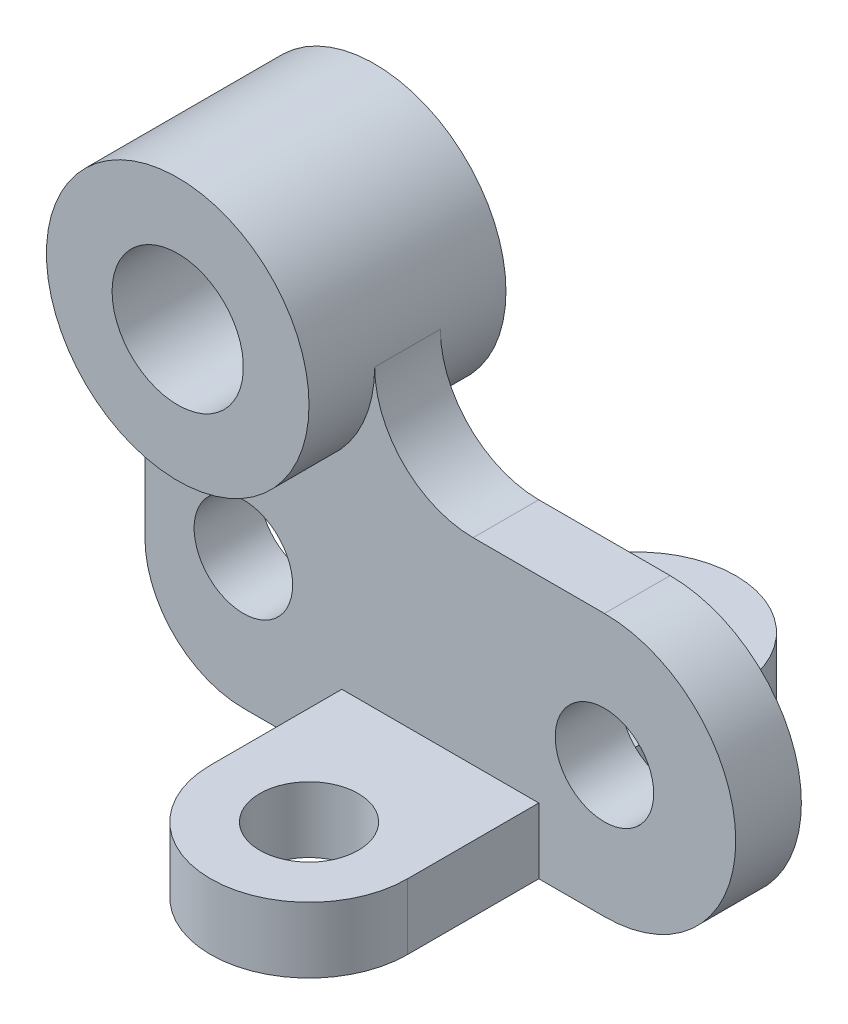
SolidWorks part; units mm, degrees
ref_plane "Front Plane" through (0, 0, 0) normal (0, 0, 1) x (1, 0, 0)
ref_plane "Top Plane" through (0, 0, 0) normal (0, 1, 0) x (1, 0, 0)
ref_plane "Right Plane" through (0, 0, 0) normal (1, 0, 0) x (0, 0, -1)
sketch "Sketch2" plane through (0, 0, 0) normal (0, 0, 1) x (1, 0, 0)
  line L0 (-19.05, -16.8005) -> (-19.05, -50.8)
  line L1 (0, -69.85) -> (69.85, -69.85)
  line L2 (44.45, -19.05) -> (69.85, -19.05)
  circle A0 centre (0, 0) radius 12.7
  circle A1 centre (0, 0) radius 25.4
  arc A2 (44.45, -19.05) -> (25.4, 0) centre (44.45, 0) cw
  arc A3 (69.85, -19.05) -> (69.85, -69.85) centre (69.85, -44.45) cw
  circle A4 centre (0, -44.45) radius 9.525
  circle A5 centre (69.85, -44.45) radius 9.525
  arc A6 (-19.05, -50.8) -> (0, -69.85) centre (0, -50.8) ccw
  point P15 (0, 0)
  point P16 (-19.0845, -16.7613)
  point P17 (0, 0)
  point P18 (0, 0)
  dimension "D1" = 25.4
  dimension "D2" = 50.8
  dimension "D3" = 88.9
  dimension "D5" = 25.4
  dimension "D6" = 19.05
  dimension "D7" = 19.05
  dimension "D9" = 19.05
  dimension "D4" = 44.45
  dimension "D8" = 69.85
extrude "Boss-Extrude1" add sketch "Sketch2" along normal mid plane 12.7 contours L0 A6 L1 A3 L2 A2 A1 A4 A5 region at (37.214, -44.0002, 0)
extrude "Boss-Extrude2" add sketch "Sketch2<3>" along normal mid plane 38.1 contours A1 A0 region at (-8.7263, 23.0875, 0)
sketch "Sketch2<3>" plane through (0, 0, 0) normal (0, 0, 1) x (1, 0, 0) same geometry as "Sketch2"
sketch "Sketch3" plane through (0, -69.85, 0) normal (0, -1, 0) x (1, 0, 0)
  line L0 (38.1, -31.75) -> (38.1, 31.75) construction
  line L1 (0, 6.35) -> (69.85, 6.35) construction
  line L2 (19.05, -31.75) -> (19.05, 31.75)
  line L3 (57.15, -31.75) -> (57.15, 31.75)
  line L4 (-122.4827, 0) -> (122.4827, 0) construction
  arc A0 (19.05, -31.75) -> (57.15, -31.75) centre (38.1, -31.75) ccw
  arc A1 (57.15, 31.75) -> (19.05, 31.75) centre (38.1, 31.75) ccw
  circle A2 centre (38.1, 31.75) radius 9.525
  circle A3 centre (38.1, -31.75) radius 9.525
  point P4 (38.1, 0)
  point P13 (0, 0)
  dimension "D1" = 19.05
  dimension "D4" = 19.05
  dimension "D5" = 19.05
  dimension "D2" = 25.4
  dimension "D3" = 38.1
extrude "Boss-Extrude3" add sketch "Sketch3" against normal blind 12.7
